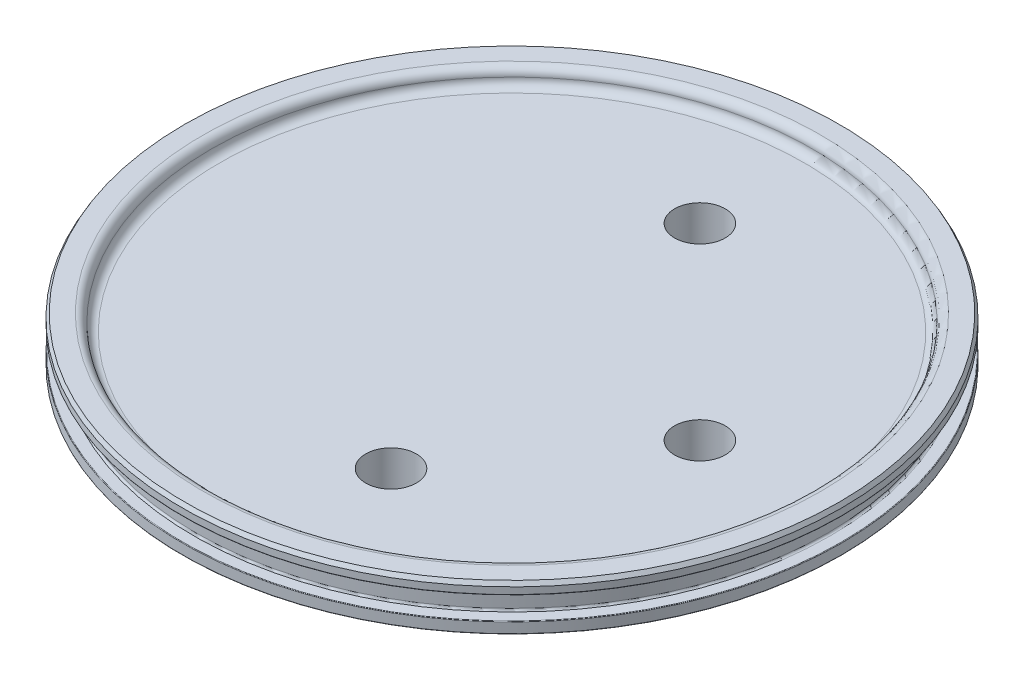
SolidWorks part; units mm, degrees
material "6061-T6 (SS)"
ref_plane "Front Plane" through (0, 0, 0) normal (0, 0, 1) x (1, 0, 0)
ref_plane "Top Plane" through (0, 0, 0) normal (0, 1, 0) x (1, 0, 0)
ref_plane "Right Plane" through (0, 0, 0) normal (1, 0, 0) x (0, 0, -1)
sketch "Sketch1" plane through (0, 0, 0) normal (0, 0, 1) x (1, 0, 0)
  line L0 (0, 48.1922) -> (0, -25.6743) construction
  line L1 (0, 0) -> (72.39, 0)
  line L2 (72.39, 0) -> (72.39, 2.4638)
  line L3 (72.39, 2.4638) -> (69.469, 2.4638)
  line L4 (69.469, 2.4638) -> (69.469, 7.4422)
  line L5 (69.469, 7.4422) -> (72.39, 7.4422)
  line L6 (72.39, 7.4422) -> (72.39, 9.906)
  line L7 (72.39, 9.906) -> (66.04, 9.906)
  line L8 (66.04, 9.906) -> (66.04, 6.35)
  line L9 (66.04, 6.35) -> (0, 6.35)
  line L10 (0, 6.35) -> (0, 0)
  dimension "D1" = 144.78
  dimension "D2" = 4.9784
  dimension "D3" = 2.921
  dimension "D5" = 6.35
  dimension "D6" = 6.35
  dimension "D4" = 9.906
revolve "Revolve1" add sketch "Sketch1" angle 360 about L0
sketch "Sketch6" plane through (0, 0, 0) normal (0, -1, 0) x (1, 0, 0)
  circle A0 centre (0, 0) radius 66.04
  dimension "D1" = 132.08
extrude "Boss-Extrude1" add sketch "Sketch6" along normal blind 2.54
hole_wizard "Pipe Tap Drill for 1/4 Tap - GN2" positions "Sketch2" profile "Sketch3" hole size "1/4" standard "ANSI Inch" end condition through all
sketch "Sketch2" plane through (0, 6.35, 0) normal (0, 1, 0) x (1, 0, 0)
  line L3 (0, 41.275) -> (0, 0) construction
  line L4 (0, 0) -> (41.275, 0) construction
  line L6 (0, 0) -> (12.7, -39.2726) construction
  point P41 (12.7, -39.2726)
  point P44 (0, 41.275)
  point P47 (41.275, 0)
  dimension "D1" = 41.275
  dimension "D2" = 41.275
  dimension "D3" = 41.275
  dimension "D4" = 12.7
sketch "Sketch3" plane through (12.7, 6.35, 39.2726) normal (1, 0, 0) x (0, 0, 1)
  line L0 (0, 0) -> (0, 8.89)
  line L1 (0, 8.89) -> (5.5626, 8.89)
  line L2 (5.5626, 8.89) -> (5.5626, 0)
  line L5 (5.5626, 0) -> (0, 0)
  line L11 (0, -6.35) -> (0, 107.95) construction
  dimension "Thru Hole Dia." = 11.1252
  dimension "Thru Hole Depth" = 8.89
fillet "CNC ID Fillet" radius 0.4064 3 edges at (-69.469, 7.4422, 0) (-69.469, 2.4638, 0) (66.04, 0, 0)
fillet "CNC OD Fillet" radius 0.127 4 edges at (-72.39, 7.4422, 0) (-72.39, 2.4638, 0) (66.04, -2.54, 0) (-72.39, 0, 0)
chamfer "CNC Chamfers" distance 0.508 angle 60 1 edges at (-72.39, 9.906, 0) first distance on face at (-66.04, 9.906, 0)
fillet "CNC Bore Fillet" radius 1.778 2 edges at (-66.04, 6.35, 0) (-66.04, 9.906, 0)
equation "\"D3@Sketch1\"=(5.7-5.47)/2"
